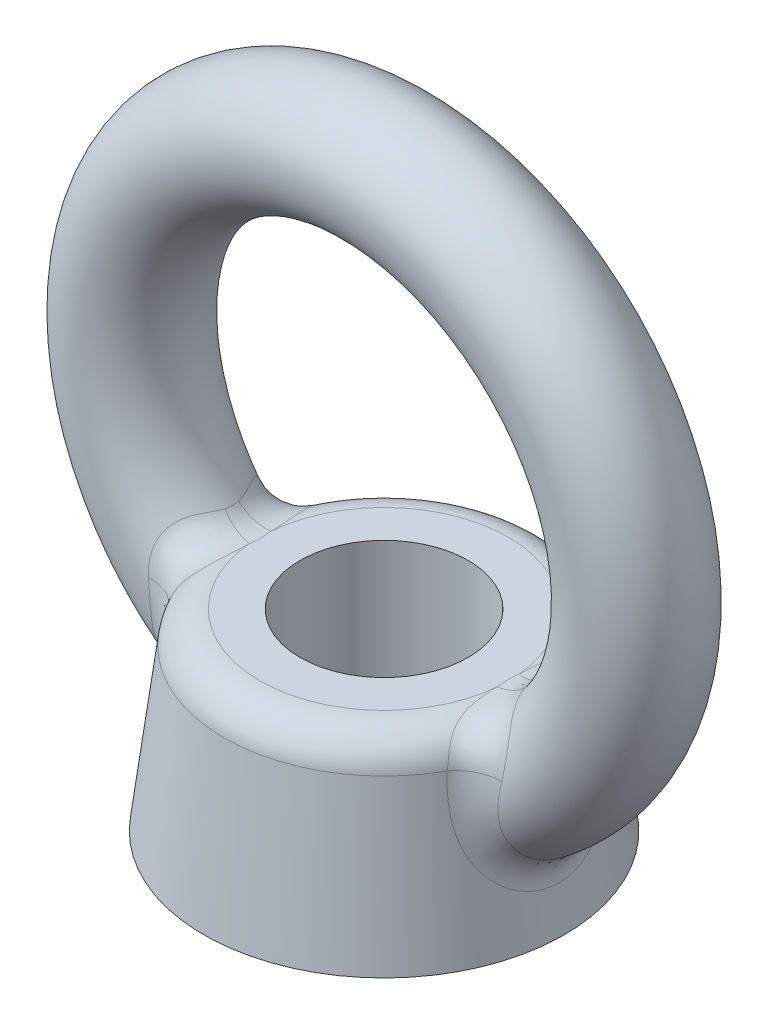
SolidWorks part; units mm, degrees
material "Латунь"
ref_plane "Спереди" through (0, 0, 0) normal (0, 0, 1) x (1, 0, 0)
ref_plane "Сверху" through (0, 0, 0) normal (0, 1, 0) x (1, 0, 0)
ref_plane "Справа" through (0, 0, 0) normal (1, 0, 0) x (0, 0, -1)
sketch "Эскиз2" plane through (0, 0, 0) normal (0, 0, 1) x (1, 0, 0)
  line L1 (0, -8.5141) -> (0, 57.16) construction
  line L5 (0, 0) -> (15, 0)
  line L6 (15, 0) -> (13.3285, 13.3721)
  line L7 (10.3517, 16) -> (0, 16)
  line L8 (0, 16) -> (0, 0)
  arc A0 (13.3285, 13.3721) -> (10.3517, 16) centre (10.3517, 13) ccw
  point P10 (13, 16)
  dimension "D4" = 3
  dimension "D1" = 30
  dimension "D2" = 26
  dimension "D3" = 16
revolve "Повернуть1" add sketch "Эскиз2" angle 360 about L1
sketch "Эскиз3" plane through (0, 0, 0) normal (1, 0, 0) x (0, 0, -1)
  circle A0 centre (0, 11) radius 5
  dimension "D2" = 10
  dimension "D1" = 11
sketch "Эскиз4" plane through (0, 0, 0) normal (0, 0, 1) x (1, 0, 0)
  line L5 (-19.2796, 15.1447) -> (-30.0344, 34.6989)
  line L6 (-20.396, 51) -> (20.396, 51)
  line L7 (0, 0) -> (0, 60.7) construction
  line L8 (19.2796, 15.1447) -> (30.0344, 34.6989)
  line L9 (-12.2698, 11) -> (12.2698, 11)
  arc A4 (-20.396, 51) -> (-30.0344, 34.6989) centre (-20.396, 40) ccw
  arc A5 (30.0344, 34.6989) -> (20.396, 51) centre (20.396, 40) ccw
  arc A6 (12.2698, 11) -> (19.2796, 15.1447) centre (12.2698, 19) ccw
  arc A7 (-19.2796, 15.1447) -> (-12.2698, 11) centre (-12.2698, 19) ccw
  point P5 (-39, 51)
  point P13 (-17, 11)
  point P14 (17, 11)
  point P15 (39, 51)
  dimension "D1" = 11
  dimension "D6" = 8
  dimension "D2" = 78
  dimension "D3" = 34
  dimension "D4" = 40
  dimension "D5" = 11
sweep "По траектории1" [suppressed] add profiles "Эскиз3" path "Эскиз4"
fillet "Скругление1" [suppressed] radius 3
sketch "Эскиз7" plane through (0, 0, 0) normal (1, 0, 0) x (0, 0, -1)
  line L0 (-15, 0) -> (15, 0) construction
  line L3 (9.3598, 27) -> (-12.1065, 27) construction
  circle A0 centre (0, 6) radius 5
  dimension "D1" = 10
  dimension "D2" = 6
  dimension "D3" = 21
revolve "Повернуть3" add sketch "Эскиз7" angle 360 about L3
fillet "Скругление2" radius 3 4 edges at (11.4884, 15.7638, 0.8319) (-11.4884, 15.7638, -0.8319) (14.3357, 5.3109, 0.1179) (-14.3357, 5.3109, -0.1179)
hole_wizard "Отверстие обработанное метчиком M161" positions "Эскиз5" profile "Эскиз6" tap size "M16" standard "ISO" end condition up to next
sketch "Эскиз5" plane through (0, 16, 0) normal (0, 1, 0) x (1, 0, 0)
  point P0 (0, 0)
sketch "Эскиз6" plane through (0, 16, 0) normal (1, 0, 0) x (0, 0, 1)
  line L0 (0, 0) -> (0, 16)
  line L1 (0, 16) -> (9, 16)
  line L2 (7, 14) -> (7, 0)
  line L5 (7, 0) -> (0, 0)
  line L7 (9, 16) -> (7, 14)
  line L8 (-9, 16) -> (-7, 14) construction
  line L11 (0, -6.35) -> (0, 107.95) construction
  dimension "Диаметр проходного сверла" = 14
  dimension "Глубина проходного сверла" = 16
  dimension "Диаметр задней зенковки" = 18
  dimension "Угол задней зенковки" = 90
cosmetic thread "Отверстие резьбы2" parameters "D2"=16
